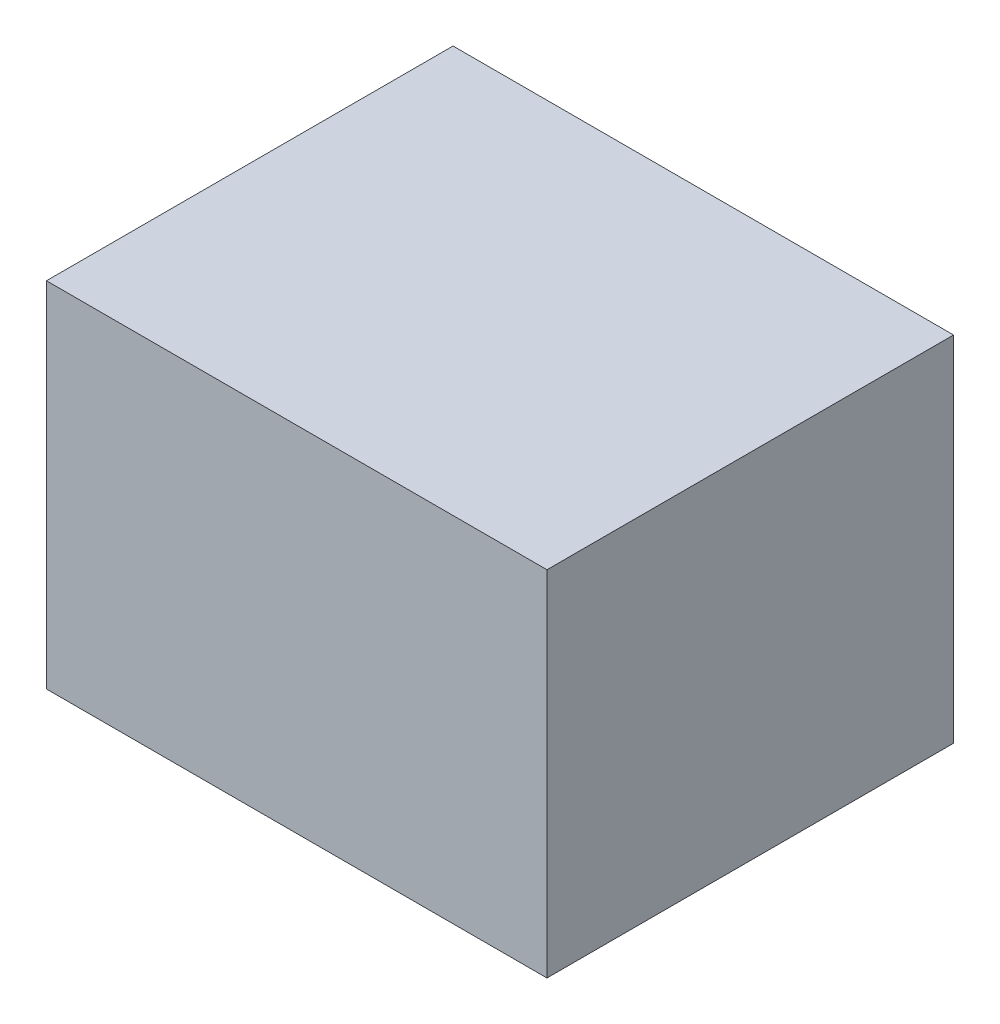
SolidWorks part; units mm, degrees
ref_plane "Front Plane" through (0, 0, 0) normal (0, 0, 1) x (1, 0, 0)
ref_plane "Top Plane" through (0, 0, 0) normal (0, 1, 0) x (1, 0, 0)
ref_plane "Right Plane" through (0, 0, 0) normal (1, 0, 0) x (0, 0, -1)
sketch "Sketch1" plane through (0, 0, 0) normal (0, 1, 0) x (1, 0, 0)
  line L1 (0, 0) -> (36.4531, 0)
  line L2 (0, 0) -> (0, 29.6127)
  line L3 (0, 29.6127) -> (36.4531, 29.6127)
  line L4 (36.4531, 0) -> (36.4531, 29.6127)
extrude "Boss-Extrude1" add sketch "Sketch1" along normal blind 25.7503
